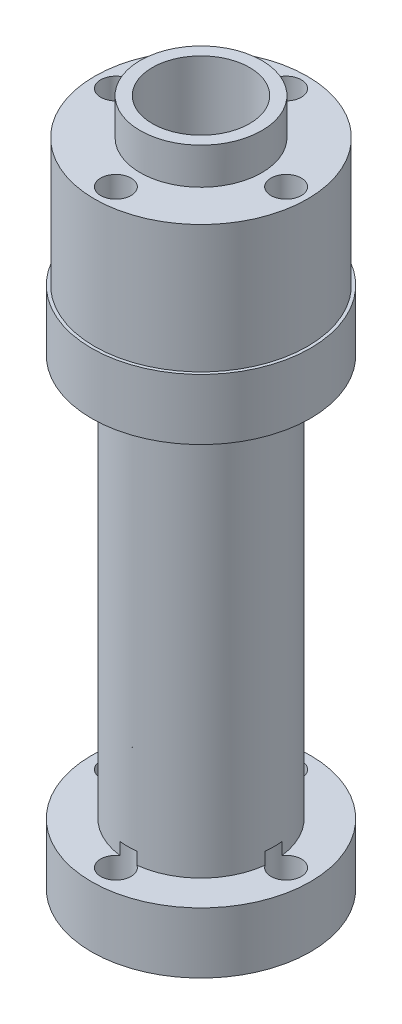
SolidWorks part; units mm, degrees
material "6061-T6 (SS)"
ref_plane "前视基准面" through (0, 0, 0) normal (0, 0, 1) x (1, 0, 0)
ref_plane "上视基准面" through (0, 0, 0) normal (0, 1, 0) x (1, 0, 0)
ref_plane "右视基准面" through (0, 0, 0) normal (1, 0, 0) x (0, 0, -1)
sketch "草图1" plane through (0, 0, 0) normal (0, 0, 1) x (1, 0, 0)
  line L0 (0, 0) -> (0, 22.2724) construction
  line L1 (-9, 38) -> (-6, 38)
  line L2 (-4, 0) -> (-9, 0)
  line L3 (-4, 0) -> (-4, 53.5)
  line L4 (-4, 53.5) -> (-8.75, 53.5)
  line L5 (-9, 0) -> (-9, 5)
  line L6 (-6, 38) -> (-6, 5)
  line L7 (-6, 5) -> (-9, 5)
  line L8 (-9, 38) -> (-9, 43)
  line L9 (-9, 43) -> (-8.75, 43)
  line L10 (-8.75, 43) -> (-8.75, 53.5)
  dimension "D1" = 8
  dimension "D2" = 18
  dimension "D3" = 15.5
  dimension "D4" = 38
  dimension "D5" = 5
  dimension "D6" = 2
  dimension "D7" = 5
  dimension "D8" = 0.25
revolve "旋转1" add sketch "草图1" angle 360 about L0
sketch "草图2" plane through (0, 53.5, 0) normal (0, 1, 0) x (1, 0, 0)
  circle A0 centre (0, 0) radius 7 construction
  circle A1 centre (0, 7) radius 1.25
  circle A3 centre (7, 0) radius 1.25
  circle A4 centre (0, -7) radius 1.25
  circle A5 centre (-7, 0) radius 1.25
  dimension "D1" = 14
  dimension "D2" = 2.5
  dimension "D3" = 4
extrude "切除-拉伸1" cut sketch "草图2" against normal blind 10
cosmetic thread "装饰螺纹线3" parameters "D2"=3
cosmetic thread "装饰螺纹线4" parameters "D2"=3
cosmetic thread "装饰螺纹线5" parameters "D2"=3
cosmetic thread "装饰螺纹线6" parameters "D2"=3
extrude "切除-拉伸2" cut sketch "草图2<2>" along normal blind 6 from surface starting at face at (0, 0, -4)
sketch "草图2<2>" plane through (0, 53.5, 0) normal (0, 1, 0) x (1, 0, 0) same geometry as "草图2"
cosmetic thread "装饰螺纹线1" parameters "D2"=3
cosmetic thread "装饰螺纹线7" parameters "D2"=3
cosmetic thread "装饰螺纹线8" parameters "D2"=3
cosmetic thread "装饰螺纹线9" parameters "D2"=3
sketch "草图4" plane through (0, 53.5, 0) normal (0, 1, 0) x (1, 0, 0)
  circle A0 centre (0, 0) radius 5
  circle A1 centre (0, 0) radius 4 construction
  circle A2 centre (0, 0) radius 4
  dimension "D1" = 10
extrude "凸台-拉伸1" add sketch "草图4" along normal blind 3
